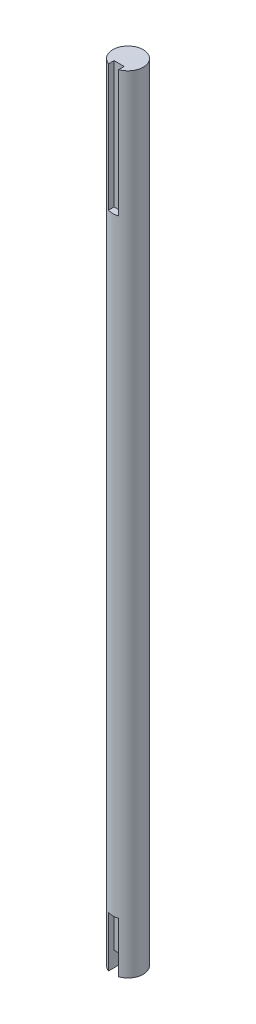
SolidWorks part; units mm, degrees
ref_plane "Front Plane" through (0, 0, 0) normal (0, 0, 1) x (1, 0, 0)
ref_plane "Top Plane" through (0, 0, 0) normal (0, 1, 0) x (1, 0, 0)
ref_plane "Right Plane" through (0, 0, 0) normal (1, 0, 0) x (0, 0, -1)
sketch "Sketch1" plane through (0, 0, 0) normal (0, 1, 0) x (1, 0, 0)
  circle A0 centre (0, 0) radius 6
  dimension "D1" = 12
extrude "Boss-Extrude1" add sketch "Sketch1" along normal blind 254 and the other way blind 56
sketch "Sketch2" plane through (0, 0, 0) normal (0, 1, 0) x (1, 0, 0)
  line L1 (-2, -8.5) -> (2, -8.5)
  line L2 (-2, -8.5) -> (-2, -3.5)
  line L3 (-2, -3.5) -> (2, -3.5)
  line L4 (2, -8.5) -> (2, -3.5)
  line L5 (-2, -8.5) -> (2, -3.5) construction
  line L6 (-2, -3.5) -> (2, -8.5) construction
  circle A0 centre (0, 0) radius 6 construction
  point P0 (0, -6)
  dimension "D1" = 2.5
  dimension "D2" = 4
extrude "Cut-Extrude3" cut sketch "Sketch2" against normal blind 0.0001 and the other way blind 20 from surface starting at face at (0, -56, 6)
extrude "Cut-Extrude4" cut sketch "Sketch2<2>" against normal blind 50 from surface starting at face at (0, 254, 6)
sketch "Sketch2<2>" plane through (0, 0, 0) normal (0, 1, 0) x (1, 0, 0) same geometry as "Sketch2"
sketch "Sketch3" plane through (0, 0, 0) normal (0, 1, 0) x (1, 0, 0)
  line L1 (-2, -11) -> (2, -11)
  line L2 (-2, -11) -> (-2, -1)
  line L3 (-2, -1) -> (2, -1)
  line L4 (2, -11) -> (2, -1)
  line L5 (-2, -11) -> (2, -1) construction
  line L6 (-2, -1) -> (2, -11) construction
  arc A0 (-2, -5.6569) -> (2, -5.6569) centre (0, 0) ccw construction
  point P0 (0, -6)
  dimension "D1" = 4
  dimension "D2" = 5
extrude "Cut-Extrude6" cut sketch "Sketch3" along normal blind 6 from surface starting at face at (0, -56, 1.6642)
sketch "Sketch5" plane through (0, 0, 0) normal (1, 0, 0) x (0, 0, -1)
  line L0 (0, 259.1669) -> (0, -132.9751) construction
